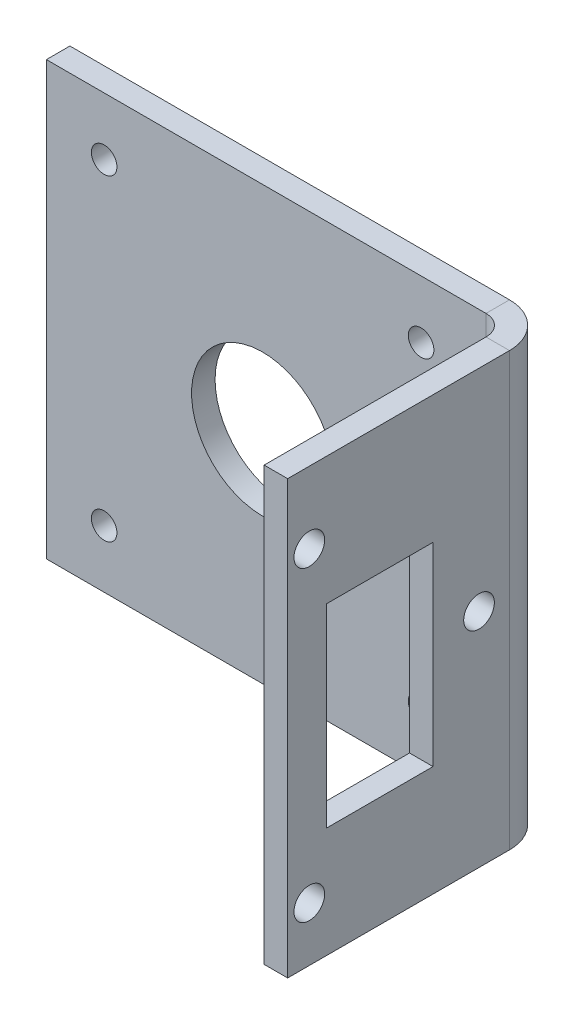
SolidWorks part; units mm, degrees
note: The reader was unsure of these and kept them because the rebuilt part matched: flange length of "Edge-Flange1".
ref_plane "Front Plane" through (0, 0, 0) normal (0, 0, 1) x (1, 0, 0)
ref_plane "Top Plane" through (0, 0, 0) normal (0, 1, 0) x (1, 0, 0)
ref_plane "Right Plane" through (0, 0, 0) normal (1, 0, 0) x (0, 0, -1)
sketch "Sketch1" plane through (0, 0, 0) normal (0, 0, 1) x (1, 0, 0)
  line L1 (0, 0) -> (47.3, 0)
  line L2 (0, 0) -> (0, 42.3)
  line L3 (0, 42.3) -> (47.3, 42.3)
  line L4 (47.3, 0) -> (47.3, 42.3)
  line L5 (0, 0) -> (47.3, 42.3) construction
  line L6 (0, 42.3) -> (47.3, 0) construction
  point P4 (23.65, 21.15)
  dimension "D1" = 42.3
  dimension "D2" = 47.3
base flange "Base-Flange1" sketch "Sketch1" thickness 2.3 reverse thickness direction no parameters "D1"=2
edge flange "Edge-Flange1" sketch "Sketch8" flange angle 90 flange length 26 flange position material inside bend radius 2 thickness 2.3 relief rectangular parameters "D6"=10
sketch "Sketch8" plane through (47.3, 0, 0) normal (-1, 0, 0) x (0, -1, 0)
  line L2 (-42.3, 0) -> (-42.3, 23.7)
  line L3 (-42.3, 23.7) -> (0, 23.7)
  line L4 (0, 23.7) -> (0, 0)
  line L5 (0, 0) -> (-42.3, 0) construction
  line L6 (0, 0) -> (-42.3, 0)
bend "EdgeBend1" bend radius 2 bend angle 90 parameters "D5"=1
extrude "Cut-Extrude1" cut sketch "Sketch9" against normal blind 3
sketch "Sketch9" plane through (47.3, -232.998, -457.7031) normal (1, 0, 0) x (0, 0, -1)
  line L1 (-467.1848, 262.798) -> (-477.5848, 262.798)
  line L2 (-467.1848, 262.798) -> (-467.1848, 243.798)
  line L3 (-467.1848, 243.798) -> (-477.5848, 243.798)
  line L4 (-477.5848, 262.798) -> (-477.5848, 243.798)
  line L5 (-467.1848, 262.798) -> (-477.5848, 243.798) construction
  line L6 (-467.1848, 243.798) -> (-477.5848, 262.798) construction
  point P4 (-472.3848, 253.298)
extrude "Cut-Extrude2" cut sketch "Sketch10" against normal blind 3
sketch "Sketch10" plane through (47.3, -232.998, -457.7031) normal (1, 0, 0) x (0, 0, -1)
  circle A0 centre (-479.2848, 268.298) radius 1.5
  circle A1 centre (-462.6848, 254.698) radius 1.5
  circle A2 centre (-479.2848, 238.298) radius 1.5
sketch "Sketch11" plane through (0, 0, 0) normal (0, 0, 1) x (1, 0, 0)
  circle A0 centre (5.65, 5.65) radius 1.25 construction
  circle A1 centre (5.65, 36.65) radius 1.25 construction
  circle A2 centre (5.65, 5.65) radius 1.25
  circle A3 centre (5.65, 36.65) radius 1.25
  circle A4 centre (36.65, 5.65) radius 1.25 construction
  circle A5 centre (36.65, 36.65) radius 1.25 construction
  circle A6 centre (36.65, 5.65) radius 1.25
  circle A7 centre (36.65, 36.65) radius 1.25
extrude "Cut-Extrude5" cut sketch "Sketch11" against normal blind 3 normal cut yes
sketch "Sketch22" plane through (0, 0, 0) normal (0, 0, 1) x (1, 0, 0)
  circle A0 centre (21.15, 21.15) radius 6.95 construction
  circle A1 centre (21.15, 21.15) radius 6.95
extrude "Cut-Extrude6" cut sketch "Sketch22" against normal blind 3 normal cut yes
sketch "Bend-Lines1" [suppressed] plane through (0, 0, 0) normal (0, 1, 0) x (1, 0, 0)
sketch "Bounding-Box1" [suppressed] plane through (0, 0, 0) normal (0, 1, 0) x (1, 0, 0)
sheet metal parameters "Sheet-Metal1" thickness 2.3 parameters "D1"=2
flat pattern "Flat-Pattern1" [suppressed]
sketch "Bend-Lines2" plane through (0, 0, 0) normal (0, 1, 0) x (1, 0, 0)
sketch3d "Bounding-Box2" [suppressed]
  line L0 (0, 0, 0) -> (-47.3, 0, 0) construction
  line L1 (0, 42.3, 0) -> (-47.3, 42.3, 0) construction
  line L2 (0, 0, 0) -> (0, 42.3, 0) construction
  line L3 (-47.3, 0, 0) -> (-47.3, 42.3, 0) construction
sheet metal parameters "Sheet-Metal2" thickness 2.3 parameters "D1"=2
flat pattern "Flat-Pattern1"
sketch "Bend-Lines2" plane through (0, 0, 0) normal (0, 0, 1) x (1, 0, 0)
  line L0 (45.474, 0) -> (45.474, 42.3) construction
  line L1 (45.474, 0) -> (45.474, 42.3) construction
sketch3d "Bounding-Box2" [suppressed]
  line L0 (0, 0, 0) -> (69.648, 0, 0) construction
  line L1 (0, 42.3, 0) -> (69.648, 42.3, 0) construction
  line L2 (0, 0, 0) -> (0, 42.3, 0) construction
  line L3 (69.648, 0, 0) -> (69.648, 42.3, 0) construction
bend of the flat pattern "Flatten-<EdgeBend1>1"
sheet metal parameters "Sheet-Metal3" thickness 2.3 parameters "D1"=2
flat pattern "Flat-Pattern1"
sketch "Bend-Lines2" plane through (0, 0, 0) normal (0, 0, 1) x (1, 0, 0)
  line L0 (45.474, 0) -> (45.474, 42.3) construction
  line L1 (45.474, 0) -> (45.474, 42.3) construction
sketch3d "Bounding-Box2" [suppressed]
  line L0 (0, 0, 0) -> (69.648, 0, 0) construction
  line L1 (0, 42.3, 0) -> (69.648, 42.3, 0) construction
  line L2 (0, 0, 0) -> (0, 42.3, 0) construction
  line L3 (69.648, 0, 0) -> (69.648, 42.3, 0) construction
bend of the flat pattern "Flatten-<EdgeBend1>1"
sheet metal parameters "Sheet-Metal4" thickness 2.3 parameters "D1"=2
flat pattern "Flat-Pattern1"
sketch "Bend-Lines2" plane through (0, 0, 0) normal (0, 0, 1) x (1, 0, 0)
  line L0 (45.474, 0) -> (45.474, 42.3) construction
  line L1 (45.474, 0) -> (45.474, 42.3) construction
sketch3d "Bounding-Box2" [suppressed]
  line L0 (0, 0, 0) -> (69.648, 0, 0) construction
  line L1 (0, 42.3, 0) -> (69.648, 42.3, 0) construction
  line L2 (0, 0, 0) -> (0, 42.3, 0) construction
  line L3 (69.648, 0, 0) -> (69.648, 42.3, 0) construction
bend of the flat pattern "Flatten-<EdgeBend1>1"
sheet metal parameters "Sheet-Metal10" thickness 2.3 parameters "D1"=2
flat pattern "Flat-Pattern1"
sketch "Bend-Lines2" plane through (0, 0, 0) normal (0, 0, 1) x (1, 0, 0)
  line L0 (45.474, 0) -> (45.474, 42.3) construction
  line L1 (45.474, 0) -> (45.474, 42.3) construction
sketch3d "Bounding-Box2" [suppressed]
  line L0 (0, 0, 0) -> (69.648, 0, 0) construction
  line L1 (0, 42.3, 0) -> (69.648, 42.3, 0) construction
  line L2 (0, 0, 0) -> (0, 42.3, 0) construction
  line L3 (69.648, 0, 0) -> (69.648, 42.3, 0) construction
bend of the flat pattern "Flatten-<EdgeBend1>1"
sheet metal parameters "Sheet-Metal11" thickness 2.3 parameters "D1"=2
flat pattern "Flat-Pattern1"
sketch "Bend-Lines2" plane through (0, 0, 0) normal (0, 0, 1) x (1, 0, 0)
  line L0 (45.474, 0) -> (45.474, 42.3) construction
  line L1 (45.474, 0) -> (45.474, 42.3) construction
sketch3d "Bounding-Box2" [suppressed]
  line L0 (0, 0, 0) -> (69.648, 0, 0) construction
  line L1 (0, 42.3, 0) -> (69.648, 42.3, 0) construction
  line L2 (0, 0, 0) -> (0, 42.3, 0) construction
  line L3 (69.648, 0, 0) -> (69.648, 42.3, 0) construction
bend of the flat pattern "Flatten-<EdgeBend1>1"
